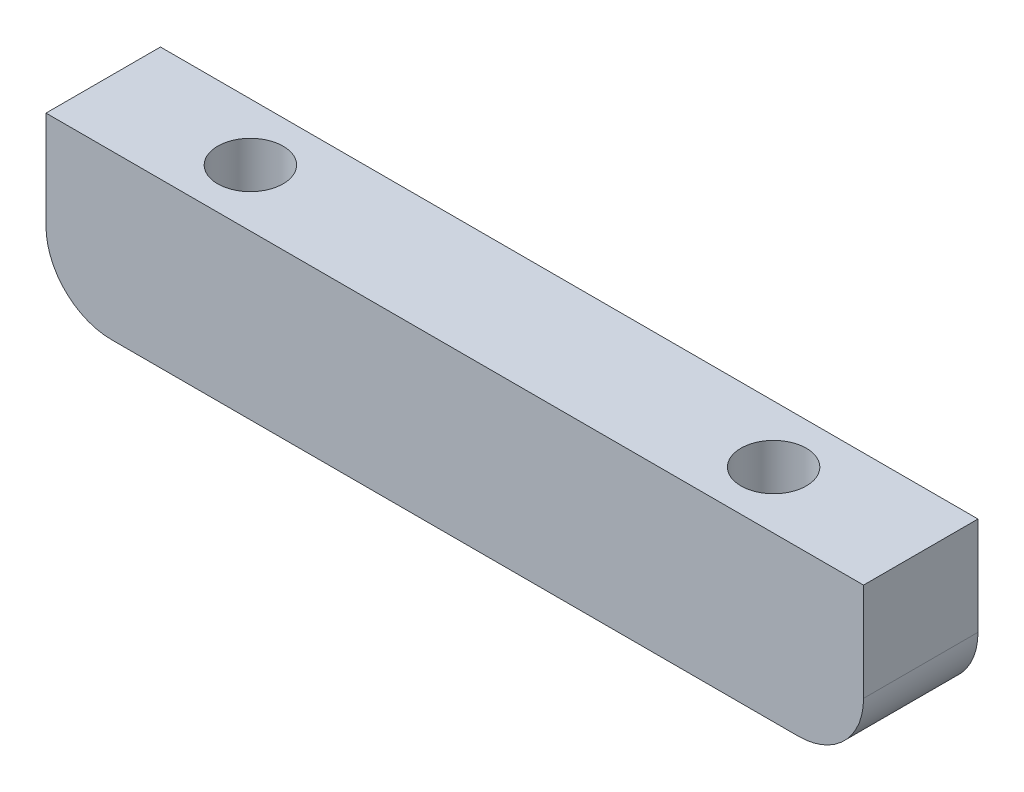
SolidWorks part; units mm, degrees
ref_plane "Front Plane" through (0, 0, 0) normal (0, 0, 1) x (1, 0, 0)
ref_plane "Top Plane" through (0, 0, 0) normal (0, 1, 0) x (1, 0, 0)
ref_plane "Right Plane" through (0, 0, 0) normal (1, 0, 0) x (0, 0, -1)
sketch "Sketch1" plane through (0, 0, 0) normal (0, 1, 0) x (1, 0, 0)
  line L1 (-25, 3.5) -> (25, 3.5)
  line L2 (-25, 3.5) -> (-25, -3.5)
  line L3 (-25, -3.5) -> (25, -3.5)
  line L4 (25, 3.5) -> (25, -3.5)
  line L5 (-25, 3.5) -> (25, -3.5) construction
  line L6 (-25, -3.5) -> (25, 3.5) construction
  point P0 (0, 0)
  dimension "D1" = 50
  dimension "D2" = 7
extrude "Boss-Extrude1" add sketch "Sketch1" along normal blind 10
sketch "Sketch2" plane through (0, 10, 0) normal (0, 1, 0) x (1, 0, 0)
  line L0 (0, 3.5) -> (0, -3.5) construction
  line L1 (25, 3.5) -> (-25, 3.5) construction
  line L2 (-25, -3.5) -> (25, -3.5) construction
  line L3 (-25, 0) -> (25, 0) construction
  line L4 (-25, 3.5) -> (-25, -3.5) construction
  line L5 (25, -3.5) -> (25, 3.5) construction
  circle A1 centre (16, 0) radius 2
  circle A2 centre (-16, 0) radius 2
  dimension "D1" = 4
  dimension "D2" = 16
  dimension "D3" = 16
extrude "Cut-Extrude1" cut sketch "Sketch2" against normal blind 5
fillet "Fillet1" radius 4 2 edges at (-25, 0, 0) (25, 0, 0)
equation "\"D3@Sketch2\"=\"D2@Sketch2\""
